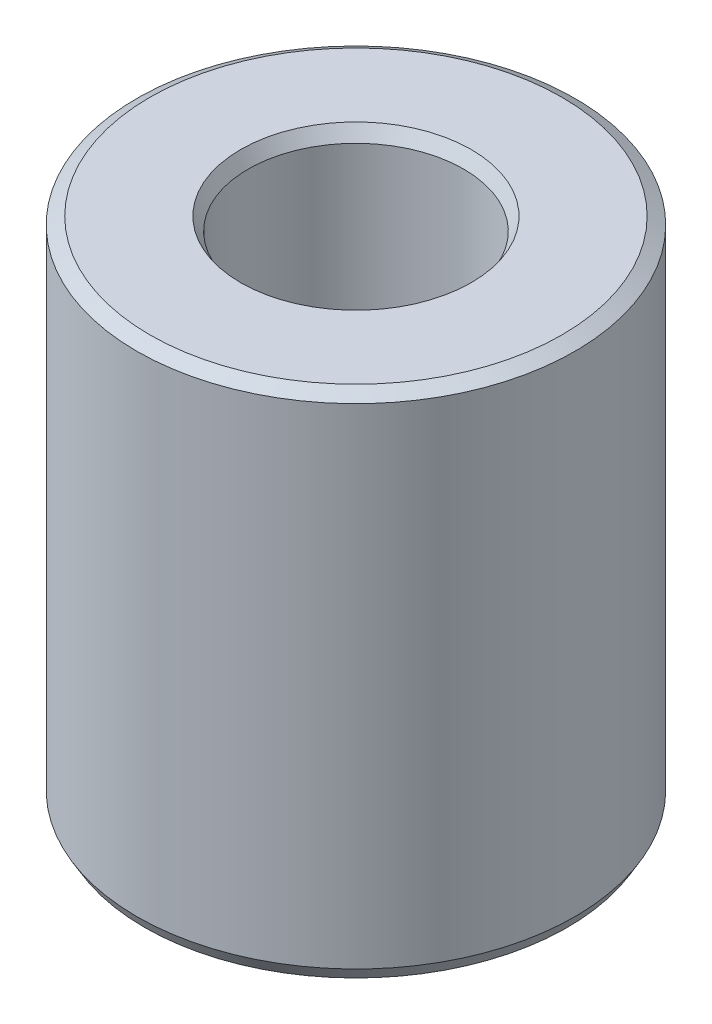
SolidWorks part; units mm, degrees
ref_plane "Front Plane" through (0, 0, 0) normal (0, 0, 1) x (1, 0, 0)
ref_plane "Top Plane" through (0, 0, 0) normal (0, 1, 0) x (1, 0, 0)
ref_plane "Right Plane" through (0, 0, 0) normal (1, 0, 0) x (0, 0, -1)
sketch "Sketch1" plane through (0, 0, 0) normal (0, 1, 0) x (1, 0, 0)
  circle A0 centre (0, 0) radius 55
  dimension "SLEEVE_OD" = 110
extrude "Boss-Extrude1" add sketch "Sketch1" along normal blind 128.134
sketch "Sketch2" plane through (0, 0, 0) normal (0, 1, 0) x (1, 0, 0)
  circle A0 centre (0, 0) radius 27.0572
  dimension "BORE_D" = 54.1143
extrude "Cut-Extrude1" cut sketch "Sketch2" along normal through all
chamfer "Chamfer1" distance 1.902 angle 60 4 edges at (0, 128.134, 27.0572) (0, 0, 27.0572) (0, 0, 55) (0, 128.134, 55) first distance on face at (0, 128.134, 27.0572) first distance on face at (0, 0, 27.0572) first distance on face at (0, 128.134, 55)
